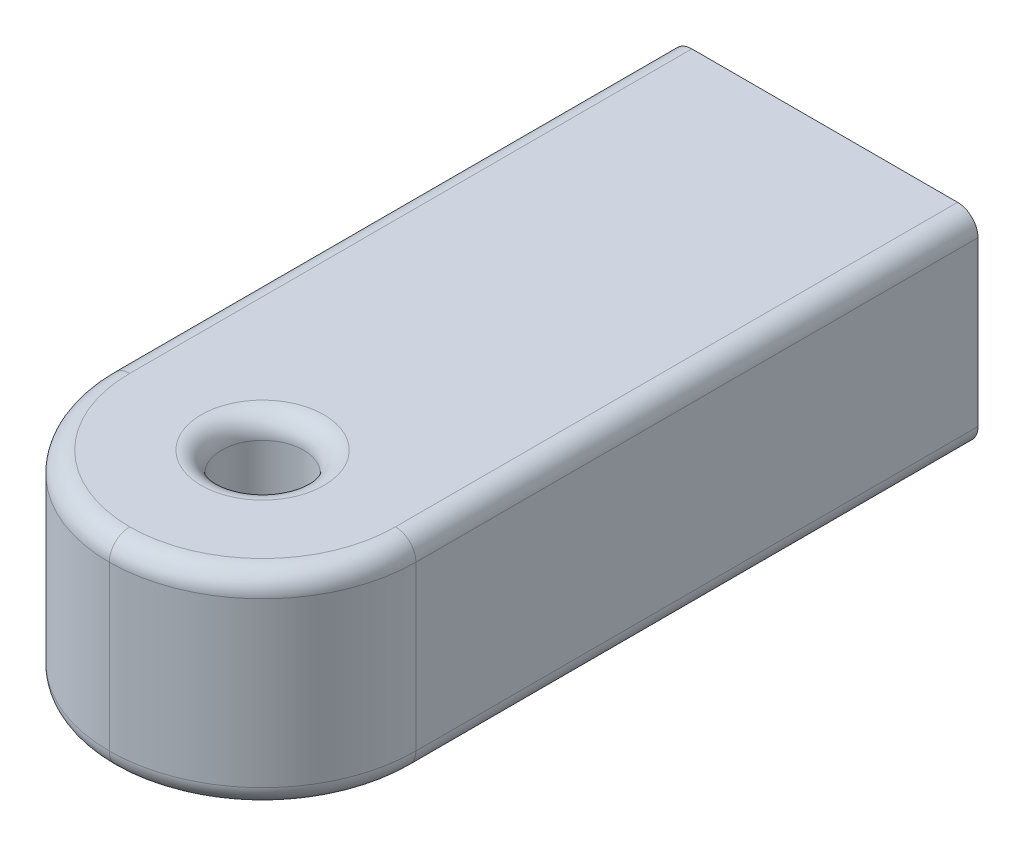
SolidWorks part; units mm, degrees
ref_plane "Front Plane" through (0, 0, 0) normal (0, 0, 1) x (1, 0, 0)
ref_plane "Top Plane" through (0, 0, 0) normal (0, 1, 0) x (1, 0, 0)
ref_plane "Right Plane" through (0, 0, 0) normal (1, 0, 0) x (0, 0, -1)
sketch "Sketch1" plane through (0, 0, 0) normal (0, 0, 1) x (1, 0, 0)
  line L1 (7.5, 5) -> (-7.5, 5)
  line L2 (7.5, 5) -> (7.5, -5)
  line L3 (7.5, -5) -> (-7.5, -5)
  line L4 (-7.5, 5) -> (-7.5, -5)
  line L5 (7.5, 5) -> (-7.5, -5) construction
  line L6 (7.5, -5) -> (-7.5, 5) construction
  point P0 (0, 0)
  dimension "D1" = 15
  dimension "D2" = 10
extrude "Boss-Extrude1" add sketch "Sketch1" along normal blind 35 contours L1 L4 L3 L2
fillet "Fillet1" radius 7.5 2 edges at (7.5, 0, 35) (-7.5, 0, 35)
sketch "Sketch2" plane through (0, 5, 0) normal (0, 1, 0) x (1, 0, 0)
  circle A0 centre (0, -27.5) radius 2
  dimension "D1" = 4
extrude "Cut-Extrude1" cut sketch "Sketch2" against normal through all both and the other way through all
fillet "Fillet2" radius 1 10 edges at (7.5, -5, 13.75) (5.3033, -5, 32.8033) (-7.5, -5, 13.75) (-7.5, 5, 13.75) (7.5, 5, 13.75) (5.3033, 5, 32.8033) (-2, -5, 27.5) (2, 5, 27.5) (-5.3033, -5, 32.8033) (-5.3033, 5, 32.8033)
